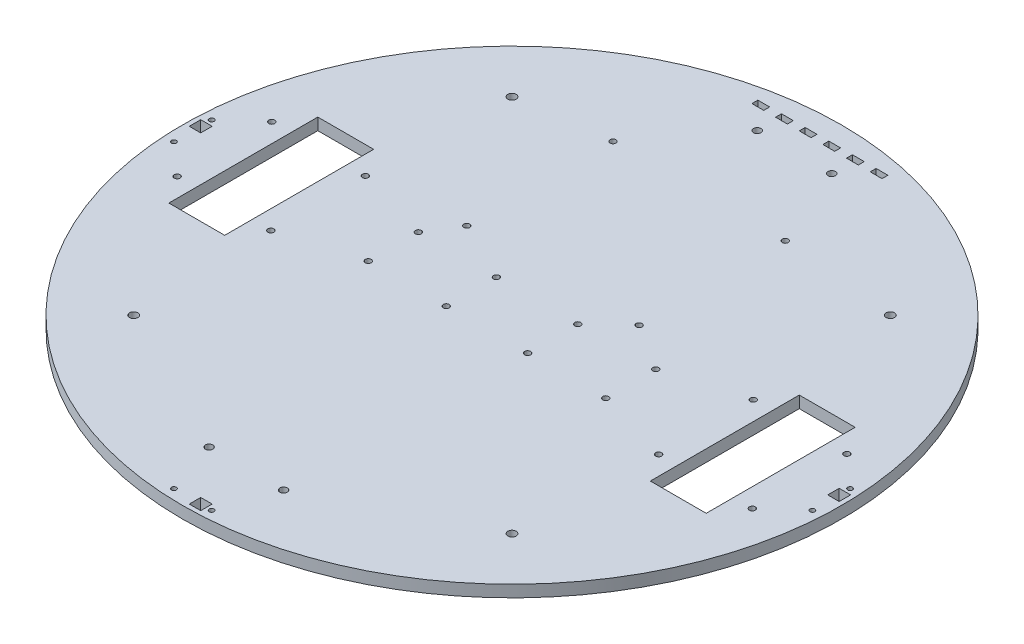
SolidWorks part; units mm, degrees
ref_plane "Front Plane" through (0, 0, 0) normal (0, 0, 1) x (1, 0, 0)
ref_plane "Top Plane" through (0, 0, 0) normal (0, 1, 0) x (1, 0, 0)
ref_plane "Right Plane" through (0, 0, 0) normal (1, 0, 0) x (0, 0, -1)
sketch "Sketch1" plane through (0, 0, 0) normal (0, 1, 0) x (1, 0, 0)
  line L0 (168.375, 7.335) -> (174.525, 7.335)
  line L1 (-144.3, 40) -> (-114.3, 40)
  line L2 (-144.3, 40) -> (-144.3, -40)
  line L3 (-144.3, -40) -> (-114.3, -40)
  line L4 (-114.3, 40) -> (-114.3, -40)
  line L13 (114.3, 40) -> (144.3, 40)
  line L14 (114.3, 40) -> (114.3, -40)
  line L15 (114.3, -40) -> (144.3, -40)
  line L16 (144.3, 40) -> (144.3, -40)
  line L17 (1.185, -168.375) -> (7.335, -168.375)
  line L18 (1.185, -168.375) -> (1.185, -174.525)
  line L19 (1.185, -174.525) -> (7.335, -174.525)
  line L20 (7.335, -168.375) -> (7.335, -174.525)
  line L21 (168.375, 7.335) -> (168.375, 1.185)
  line L22 (168.375, 1.185) -> (174.525, 1.185)
  line L23 (174.525, 7.335) -> (174.525, 1.185)
  line L24 (-174.525, 7.335) -> (-168.375, 7.335)
  line L25 (-174.525, 7.335) -> (-174.525, 1.185)
  line L26 (-174.525, 1.185) -> (-168.375, 1.185)
  line L27 (-168.375, 7.335) -> (-168.375, 1.185)
  line L28 (-21.295, 162.8645) -> (-14.945, 162.8645)
  line L29 (-33.995, 166.0395) -> (-27.645, 166.0395)
  line L30 (-33.995, 166.0395) -> (-33.995, 162.8645)
  line L31 (-33.995, 162.8645) -> (-27.645, 162.8645)
  line L32 (-27.645, 166.0395) -> (-27.645, 162.8645)
  line L33 (-14.945, 166.0395) -> (-14.945, 162.8645)
  line L34 (-21.295, 166.0395) -> (-14.945, 166.0395)
  line L35 (-21.295, 166.0395) -> (-21.295, 162.8645)
  line L36 (-8.595, 162.8645) -> (-2.245, 162.8645)
  line L37 (-2.245, 166.0395) -> (-2.245, 162.8645)
  line L38 (-8.595, 166.0395) -> (-2.245, 166.0395)
  line L39 (-8.595, 166.0395) -> (-8.595, 162.8645)
  line L40 (4.105, 162.8645) -> (10.455, 162.8645)
  line L41 (10.455, 166.0395) -> (10.455, 162.8645)
  line L42 (4.105, 166.0395) -> (10.455, 166.0395)
  line L43 (4.105, 166.0395) -> (4.105, 162.8645)
  line L44 (16.805, 162.8645) -> (23.155, 162.8645)
  line L45 (23.155, 166.0395) -> (23.155, 162.8645)
  line L46 (16.805, 166.0395) -> (23.155, 166.0395)
  line L47 (16.805, 166.0395) -> (16.805, 162.8645)
  line L48 (29.505, 162.8645) -> (35.855, 162.8645)
  line L49 (35.855, 166.0395) -> (35.855, 162.8645)
  line L50 (29.505, 166.0395) -> (35.855, 166.0395)
  line L51 (29.505, 166.0395) -> (29.505, 162.8645)
  circle A0 centre (0, 0) radius 177
  circle A1 centre (-154.46, 25.4) radius 1.6
  circle A2 centre (-154.46, -25.4) radius 1.6
  circle A3 centre (154.46, 25.4) radius 1.6
  circle A4 centre (154.46, -25.4) radius 1.6
  circle A5 centre (-104.14, 25.4) radius 1.6
  circle A6 centre (-104.14, -25.4) radius 1.6
  circle A7 centre (104.14, 25.4) radius 1.6
  circle A8 centre (104.14, -25.4) radius 1.6
  circle A9 centre (-53.7, 107.95) radius 1.6
  circle A10 centre (38.8, 107.95) radius 1.6
  circle A11 centre (-53.7, 29.45) radius 1.6
  circle A12 centre (38.8, 29.45) radius 1.6
  circle A13 centre (-101.6, -101.6) radius 2.2479
  circle A14 centre (101.6, -101.6) radius 2.2479
  circle A15 centre (-101.6, 101.6) radius 2.2479
  circle A16 centre (101.6, 101.6) radius 2.2479
  circle A17 centre (-20, -142.687) radius 2
  circle A18 centre (20, -142.687) radius 2
  circle A19 centre (-20, 151.7193) radius 2
  circle A20 centre (20, 151.7193) radius 2
  circle A21 centre (-10.125, -171.45) radius 1.3
  circle A22 centre (10.125, -171.45) radius 1.3
  circle A23 centre (171.45, -10.125) radius 1.3
  circle A24 centre (171.45, 10.125) radius 1.3
  circle A25 centre (-171.45, -10.125) radius 1.3
  circle A26 centre (-171.45, 10.125) radius 1.3
  circle A27 centre (-63.76, 13.474) radius 1.6
  circle A28 centre (-63.76, -13.45) radius 1.6
  circle A29 centre (-21.85, 13.474) radius 1.6
  circle A30 centre (-21.85, -13.45) radius 1.6
  circle A31 centre (63.76, -13.45) radius 1.6
  circle A32 centre (21.85, -13.45) radius 1.6
  circle A33 centre (21.85, 13.474) radius 1.6
  circle A34 centre (63.76, 13.474) radius 1.6
  point P9 (-114.3, 0)
  point P10 (-0.9618, 0)
  point P11 (-0.9618, 0)
  point P14 (114.3, 0)
  point P26 (-144.3, 0)
  point P27 (144.3, 0)
  dimension "D1" = 354
  dimension "D10" = 3.2
  dimension "D12" = 10.16
  dimension "D13" = 3.2
  dimension "D16" = 10.16
  dimension "D17" = 50.8
  dimension "D20" = 3.2
  dimension "D22" = 3.2
  dimension "D23" = 10.16
  dimension "D24" = 50.8
  dimension "D25" = 25.4
  dimension "D26" = 3.2
  dimension "D27" = 3.2
  dimension "D32" = 3.2
  dimension "D33" = 3.2
  dimension "D34" = 3.2
  dimension "D35" = 3.2
  dimension "D44" = 4.4958
  dimension "D45" = 4.4958
  dimension "D46" = 4.4958
  dimension "D47" = 4.4958
  dimension "D55" = 4
  dimension "D56" = 4
  dimension "D59" = 20
  dimension "D60" = 4
  dimension "D61" = 4
  dimension "D62" = 0
  dimension "D63" = 40
  dimension "D64" = 20
  dimension "D65" = 2.6
  dimension "D66" = 2.6
  dimension "D74" = 171.45
  dimension "D75" = 2.6
  dimension "D76" = 2.6
  dimension "D77" = 0
  dimension "D87" = 2.6
  dimension "D88" = 2.6
  dimension "D90" = 2.79
  dimension "D92" = 0
  dimension "D98" = 3.2
  dimension "D99" = 3.2
  dimension "D100" = 3.2
  dimension "D101" = 3.2
  dimension "D102" = 26.924
  dimension "D103" = 26.924
  dimension "D104" = 41.91
  dimension "D105" = 41.91
  dimension "D106" = 0
  dimension "D110" = 3.2
  dimension "D111" = 3.2
  dimension "D112" = 3.2
  dimension "D113" = 3.2
  dimension "D115" = 41.91
  dimension "D117" = 26.924
  dimension "D119" = 26.924
  dimension "D122" = 3.2
  dimension "D123" = 3.2
  dimension "D2" = 30
  dimension "D3" = 80
  dimension "D4" = 0
  dimension "D5" = 114.3
  dimension "D6" = 30
  dimension "D7" = 80
  dimension "D8" = 0
  dimension "D9" = 114.3
  dimension "D11" = 50.8
  dimension "D14" = 10.16
  dimension "D15" = 25.4
  dimension "D18" = 25.4
  dimension "D19" = 10.16
  dimension "D21" = 10.16
  dimension "D28" = 50.8
  dimension "D29" = 10.16
  dimension "D30" = 10.16
  dimension "D31" = 25.4
  dimension "D36" = 78.5
  dimension "D37" = 78.5
  dimension "D38" = 92.5
  dimension "D39" = 92.5
  dimension "D40" = 0
  dimension "D41" = 0
  dimension "D42" = 38.8
  dimension "D43" = 107.95
  dimension "D48" = 203.2
  dimension "D49" = 203.2
  dimension "D50" = 203.2
  dimension "D51" = 203.2
  dimension "D52" = 0
  dimension "D53" = 101.6
  dimension "D54" = 101.6
  dimension "D57" = 40
  dimension "D58" = 0
  dimension "D67" = 0
  dimension "D68" = 20.25
  dimension "D69" = 10.125
  dimension "D70" = 6.15
  dimension "D71" = 6.15
  dimension "D72" = 2.79
  dimension "D73" = 3.075
  dimension "D78" = 20.25
  dimension "D79" = 10.125
  dimension "D80" = 6.15
  dimension "D81" = 6.15
  dimension "D82" = 2.79
  dimension "D83" = 3.075
  dimension "D84" = 171.45
  dimension "D85" = 6.15
  dimension "D86" = 6.15
  dimension "D89" = 20.25
  dimension "D91" = 3.075
  dimension "D93" = 171.45
  dimension "D94" = 10.125
  dimension "D95" = 3.175
  dimension "D96" = 6.35
  dimension "D107" = 0
  dimension "D108" = 50.54
  dimension "D109" = 26.55
  dimension "D114" = 0
  dimension "D116" = 0
  dimension "D118" = 41.91
  dimension "D120" = 50.54
  dimension "D121" = 26.55
  dimension "D97" = 6
extrude "Boss-Extrude1" add sketch "Sketch1" along normal blind 6.35
